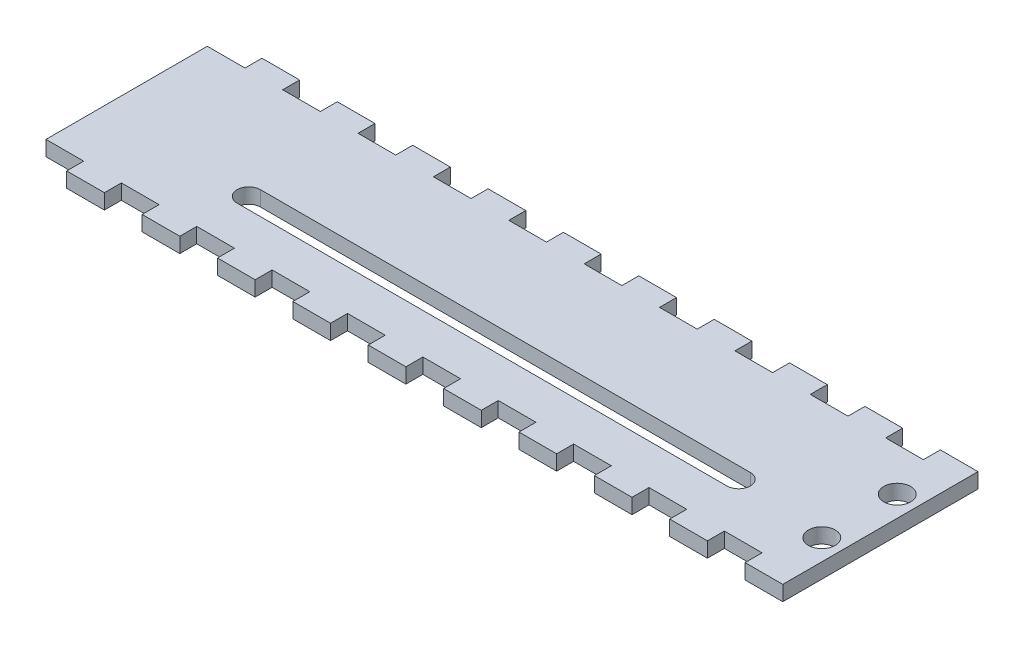
SolidWorks part; units mm, degrees
ref_plane "Front Plane" through (0, 0, 0) normal (0, 0, 1) x (1, 0, 0)
ref_plane "Top Plane" through (0, 0, 0) normal (0, 1, 0) x (1, 0, 0)
ref_plane "Right Plane" through (0, 0, 0) normal (1, 0, 0) x (0, 0, -1)
sketch "Sketch1" plane through (0, 0, 0) normal (0, 1, 0) x (1, 0, 0)
  line L0 (20, 5.35) -> (85, 5.35)
  line L1 (0, 0) -> (100, 0)
  line L2 (0, 0) -> (0, 21.4)
  line L3 (0, 21.4) -> (100, 21.4)
  line L4 (100, 0) -> (100, 21.4)
  line L5 (20, 8.45) -> (85, 8.45)
  line L6 (100, 21.4) -> (100, 23.65)
  line L7 (100, 23.65) -> (95, 23.65)
  line L8 (95, 23.65) -> (95, 21.4)
  line L9 (100, 21.4) -> (100, 23.65)
  line L10 (85, 23.65) -> (85, 21.4)
  line L11 (90, 23.65) -> (85, 23.65)
  line L12 (90, 21.4) -> (90, 23.65)
  line L13 (75, 23.65) -> (75, 21.4)
  line L14 (80, 23.65) -> (75, 23.65)
  line L15 (80, 21.4) -> (80, 23.65)
  line L16 (65, 23.65) -> (65, 21.4)
  line L17 (70, 23.65) -> (65, 23.65)
  line L18 (70, 21.4) -> (70, 23.65)
  line L19 (55, 23.65) -> (55, 21.4)
  line L20 (60, 23.65) -> (55, 23.65)
  line L21 (60, 21.4) -> (60, 23.65)
  line L22 (45, 23.65) -> (45, 21.4)
  line L23 (50, 23.65) -> (45, 23.65)
  line L24 (50, 21.4) -> (50, 23.65)
  line L25 (35, 23.65) -> (35, 21.4)
  line L26 (40, 23.65) -> (35, 23.65)
  line L27 (40, 21.4) -> (40, 23.65)
  line L28 (25, 23.65) -> (25, 21.4)
  line L29 (30, 23.65) -> (25, 23.65)
  line L30 (30, 21.4) -> (30, 23.65)
  line L31 (15, 23.65) -> (15, 21.4)
  line L32 (20, 23.65) -> (15, 23.65)
  line L33 (20, 21.4) -> (20, 23.65)
  line L34 (5, 23.65) -> (5, 21.4)
  line L35 (10, 23.65) -> (5, 23.65)
  line L36 (10, 21.4) -> (10, 23.65)
  line L37 (100, 0) -> (100, -2.25)
  line L38 (100, -2.25) -> (95, -2.25)
  line L39 (95, -2.25) -> (95, 0)
  line L40 (90, -2.25) -> (85, -2.25)
  line L41 (90, 0) -> (90, -2.25)
  line L42 (85, -2.25) -> (85, 0)
  line L43 (80, -2.25) -> (75, -2.25)
  line L44 (80, 0) -> (80, -2.25)
  line L45 (75, -2.25) -> (75, 0)
  line L46 (70, -2.25) -> (65, -2.25)
  line L47 (70, 0) -> (70, -2.25)
  line L48 (65, -2.25) -> (65, 0)
  line L49 (60, -2.25) -> (55, -2.25)
  line L50 (60, 0) -> (60, -2.25)
  line L51 (55, -2.25) -> (55, 0)
  line L52 (50, -2.25) -> (45, -2.25)
  line L53 (50, 0) -> (50, -2.25)
  line L54 (45, -2.25) -> (45, 0)
  line L55 (40, -2.25) -> (35, -2.25)
  line L56 (40, 0) -> (40, -2.25)
  line L57 (35, -2.25) -> (35, 0)
  line L58 (30, -2.25) -> (25, -2.25)
  line L59 (30, 0) -> (30, -2.25)
  line L60 (25, -2.25) -> (25, 0)
  line L61 (20, -2.25) -> (15, -2.25)
  line L62 (20, 0) -> (20, -2.25)
  line L63 (15, -2.25) -> (15, 0)
  line L64 (10, -2.25) -> (5, -2.25)
  line L65 (10, 0) -> (10, -2.25)
  line L66 (5, -2.25) -> (5, 0)
  line L67 (0, 10.7) -> (100, 10.7) construction
  circle A0 centre (20, 6.9) radius 1.55
  circle A1 centre (85, 6.9) radius 1.55
  circle A4 centre (97.23, 15.7) radius 1.78
  circle A5 centre (97.23, 5.7) radius 1.78
  dimension "D3" = 3.1
  dimension "D4" = 3.1
  dimension "D6" = 6.9
  dimension "D9" = 15
  dimension "D10" = 65
  dimension "D15" = 5
  dimension "D16" = 5
  dimension "D19" = 2.77
  dimension "D20" = 3.56
  dimension "D21" = 3.56
  dimension "D22" = 2.77
  dimension "D1" = 100
  dimension "D2" = 21.4
  dimension "D5" = 6.9
  dimension "D7" = 2.25
  dimension "D8" = 5
  dimension "D12" = 5
  dimension "D13" = 2.25
  dimension "D11" = 10
  dimension "D14" = 10
extrude "Boss-Extrude1" add sketch "Sketch1" along normal blind 2 contours L2 L67 L4 L3 | L67 L2 L1 L4 A1 L0 A0 L5 | L3 L36 L35 L34 | L3 L33 L32 L31 | L3 L30 L29 L28 | L3 L27 L26 L25 | L3 L24 L23 L22 | L3 L18 L17 L16 | L3 L21 L20 L19 | L7 L8 L3 L6 | L3 L12 L11 L10 | L3 L15 L14 L13 | L66 L64 L65 L1 | L63 L61 L62 L1 | L60 L58 L59 L1 | L57 L55 L56 L1 | L54 L52 L53 L1 | L51 L49 L50 L1 | L48 L46 L47 L1 | L45 L43 L44 L1 | L42 L40 L41 L1 | L39 L38 L37 L1 region at (49.2345, 0, -11.1157) region at (7.5, 0, 1.125) region at (7.5, 0, -22.525) region at (17.5, 0, 1.125) region at (17.5, 0, -22.525) region at (27.5, 0, 1.125) region at (27.5, 0, -22.525) region at (37.5, 0, 1.125) region at (37.5, 0, -22.525) region at (47.5, 0, 1.125) region at (47.5, 0, -22.525) region at (57.5, 0, 1.125) region at (57.5, 0, -22.525) region at (67.5, 0, 1.125) region at (67.5, 0, -22.525) region at (77.5, 0, 1.125) region at (77.5, 0, -22.525) region at (87.5, 0, 1.125) region at (87.5, 0, -22.525) region at (97.5, 0, 1.125) region at (97.5, 0, -22.525)
